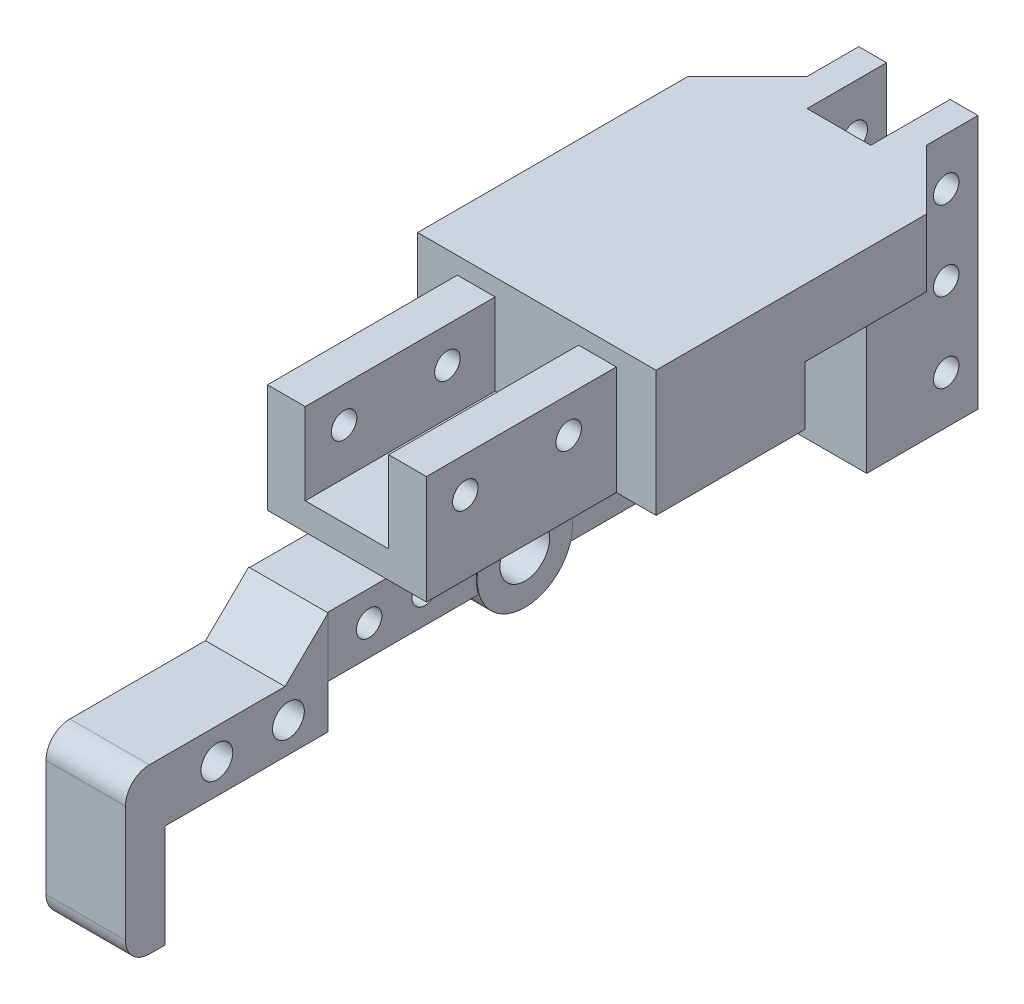
SolidWorks part; units mm, degrees
ref_plane "前视基准面" through (0, 0, 0) normal (0, 0, 1) x (1, 0, 0)
ref_plane "上视基准面" through (0, 0, 0) normal (0, 1, 0) x (1, 0, 0)
ref_plane "右视基准面" through (0, 0, 0) normal (1, 0, 0) x (0, 0, -1)
sketch "草图2" plane through (0, 0, 0) normal (1, 0, 0) x (0, 0, -1)
  line L0 (7, 0) -> (32.5, 0) construction
  line L2 (44.75, 3.775) -> (-5.25, 3.775)
  line L3 (44.75, 3.775) -> (44.75, -3.775)
  line L4 (44.75, -3.775) -> (-5.25, -3.775)
  line L5 (-5.25, 3.775) -> (-5.25, -3.775)
  line L6 (44.75, 3.775) -> (-5.25, -3.775) construction
  line L7 (44.75, -3.775) -> (-5.25, 3.775) construction
  circle A0 centre (0, 0) radius 1.6
  circle A1 centre (7, 0) radius 1.6
  circle A2 centre (32.5, 0) radius 1.6
  circle A3 centre (39.5, 0) radius 1.6
  point P9 (19.75, 0)
  dimension "D1" = 25.5
  dimension "D2" = 7
  dimension "D3" = 3.775
extrude "凸台-拉伸1" add sketch "草图2" along normal mid plane 9.8
sketch "草图3" plane through (0, 0, 0) normal (1, 0, 0) x (0, 0, -1)
  line L0 (7, 13) -> (20, 13) construction
  line L1 (2.1144, 3.775) -> (2.1144, 17.4551)
  line L2 (44.75, 3.775) -> (-5.25, 3.775) construction
  line L3 (2.1144, 17.4551) -> (26, 17.4551)
  line L4 (26, 17.4551) -> (26, 3.775)
  line L5 (26, 3.775) -> (2.1144, 3.775)
  circle A0 centre (7, 13) radius 1.6
  circle A1 centre (20, 13) radius 1.6
  point P0 (7, 0)
  point P6 (13.5, 13)
  dimension "D1" = 13
  dimension "D3" = 3.2
  dimension "D4" = 3.2
  dimension "D2" = 6
extrude "凸台-拉伸2" add sketch "草图3" along normal mid plane 20
sketch "草图4" plane through (0, 0, -2.1144) normal (0, 0, 1) x (1, 0, 0)
  line L0 (10, 17.4551) -> (-10, 17.4551) construction
  line L1 (5.25, 7.1905) -> (-5.25, 7.1905)
  line L2 (5.25, 7.1905) -> (5.25, 17.4551)
  line L3 (5.25, 17.4551) -> (-5.25, 17.4551)
  line L4 (-5.25, 7.1905) -> (-5.25, 17.4551)
  line L5 (5.25, 7.1905) -> (-5.25, 17.4551) construction
  line L6 (5.25, 17.4551) -> (-5.25, 7.1905) construction
  line L7 (0, 0) -> (0, 15.8703) construction
  point P0 (0, 12.3228)
  point P10 (0, 0)
extrude "切除-拉伸1" cut sketch "草图4" against normal through all
sketch "草图6" plane through (0, 0, 0) normal (1, 0, 0) x (0, 0, -1)
  line L0 (70, 3.6) -> (70, 13.6) construction
  line L2 (74, -12.4) -> (60, -12.4)
  line L3 (74, -12.4) -> (74, 19.6)
  line L4 (74, 19.6) -> (60, 19.6)
  line L5 (60, -12.4) -> (60, 19.6)
  line L6 (74, -12.4) -> (60, 19.6) construction
  line L7 (74, 19.6) -> (60, -12.4) construction
  circle A0 centre (70, 3.6) radius 1.6
  circle A1 centre (70, 13.6) radius 1.6
  circle A2 centre (70, -6.4) radius 1.6
  point P4 (70, 8.6)
  point P9 (67, 3.6)
  dimension "D1" = 60
  dimension "D6" = 10
  dimension "D2" = 3.6
  dimension "D3" = 10
  dimension "D4" = 4
  dimension "D5" = 14
  dimension "D7" = 6
  dimension "D8" = 6
extrude "凸台-拉伸4" add sketch "草图6" along normal mid plane 15 separate body
sketch "草图7" plane through (0, 0, -74) normal (0, 0, 1) x (1, 0, 0)
  line L0 (7.5, 19.6) -> (-7.5, 19.6) construction
  line L1 (-4, 19.6) -> (4, 19.6)
  line L2 (-4, 19.6) -> (-4, -12.4)
  line L3 (-4, -12.4) -> (4, -12.4)
  line L4 (4, 19.6) -> (4, -12.4)
  line L5 (7.5, -12.4) -> (-7.5, -12.4) construction
extrude "切除-拉伸2" cut sketch "草图7" along normal blind 10
sketch "草图8" plane through (0, 0, 0) normal (1, 0, 0) x (0, 0, -1)
  line L0 (26, 3.775) -> (26, 17.4551) construction
  line L1 (60, 19.6) -> (26, 19.6)
  line L2 (60, 19.6) -> (60, 11.1399)
  line L3 (60, 11.1399) -> (44.75, 11.1399)
  line L4 (26, 19.6) -> (26, 11.1399)
  line L7 (26, 11.1399) -> (26, 3.775)
  line L8 (26, 3.775) -> (44.75, 3.775)
  line L9 (44.75, 11.1399) -> (44.75, 3.775)
extrude "凸台-拉伸5" add sketch "草图8" along normal mid plane 30
chamfer "倒角1" distance 7.5 angle 45 2 edges at (-7.5, 15.37, -60) (7.5, 15.37, -60)
sketch "草图10" plane through (0, 0, 0) normal (1, 0, 0) x (0, 0, -1)
  line L0 (-5.25, 3.775) -> (-5.25, -9.1767)
  line L1 (-5.25, -9.1767) -> (-25.75, -9.1767)
  line L2 (-25.75, -9.1767) -> (-25.75, -22.145)
  line L3 (-30.75, -22.145) -> (-30.75, -1.5241)
  line L5 (-30.75, -22.145) -> (-25.75, -22.145)
  line L6 (-30.75, -1.5241) -> (-10.6887, -1.5241)
  line L7 (-10.6887, -1.5241) -> (-5.25, 3.775)
  circle A0 centre (-10.25, -5.4017) radius 2
  circle A1 centre (-19.25, -5.4017) radius 2
  dimension "D3" = 4
  dimension "D4" = 4
  dimension "D1" = 20.5
  dimension "D2" = 5
  dimension "D5" = 9
  dimension "D6" = 5
extrude "凸台-拉伸6" add sketch "草图10" along normal mid plane 10
fillet "圆角1" radius 3 2 edges at (0, -22.145, 30.75) (0, -1.5241, 30.75)
sketch "草图11" plane through (0, 0, 0) normal (1, 0, 0) x (0, 0, -1)
  circle A1 centre (19.4875, -2) radius 3.125
  circle A2 centre (19.4875, -2) radius 6
  dimension "D1" = 6.25
  dimension "D2" = 12
  dimension "D3" = 2
extrude "凸台-拉伸7" add sketch "草图11" along normal mid plane 10
sketch "草图12" plane through (0, 0, 0) normal (1, 0, 0) x (0, 0, -1)
  circle A0 centre (19.4875, -2) radius 3.125 construction
  circle A1 centre (19.4875, -2) radius 3.125
extrude "切除-拉伸3" cut sketch "草图12" against normal through all both and the other way through all
